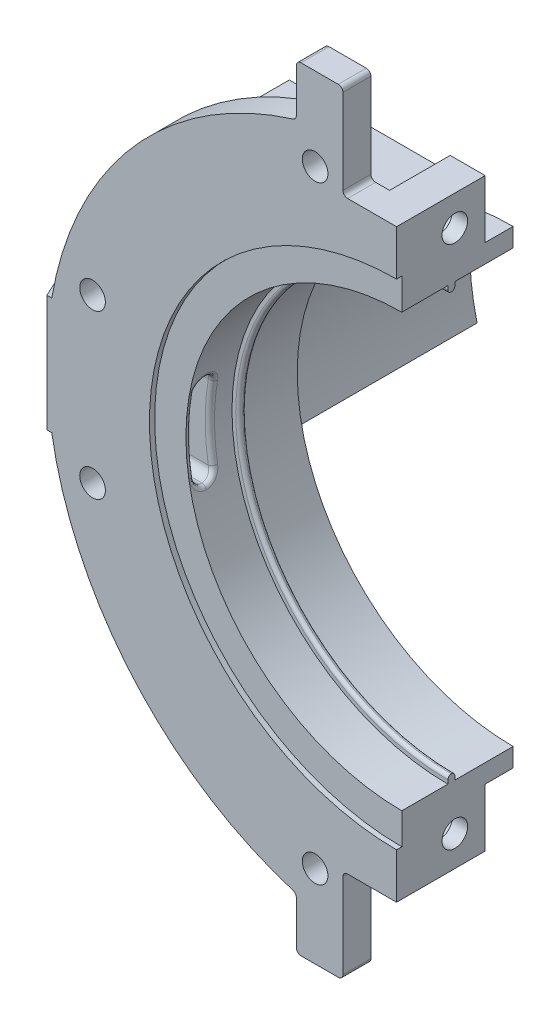
SolidWorks part; units mm, degrees
ref_plane "Front" through (0, 0, 0) normal (0, 0, 1) x (1, 0, 0)
ref_plane "Top" through (0, 0, 0) normal (0, 1, 0) x (1, 0, 0)
ref_plane "Right" through (0, 0, 0) normal (1, 0, 0) x (0, 0, -1)
sketch "Sketch1" plane through (0, 0, 0) normal (0, 0, 1) x (1, 0, 0)
  line L1 (0, 0) -> (180, 0)
  line L2 (0, 0) -> (0, 180)
  line L3 (0, 180) -> (180, 180)
  line L4 (180, 0) -> (180, 180)
  dimension "D1" = 180
extrude "Boss-Extrude1" add sketch "Sketch1" along normal blind 6
sketch "Sketch2" plane through (0, 0, 0) normal (0, 0, -1) x (-1, 0, 0)
  line L0 (0, 90) -> (-180, 90) construction
  line L1 (0, 180) -> (0, 0) construction
  line L3 (-180, 0) -> (-180, 180) construction
  circle A0 centre (-90, 90) radius 46.3
  circle A1 centre (-90, 90) radius 50.3
  point P11 (-90, 90)
  dimension "D1" = 92.6
  dimension "D2" = 4
extrude "Boss-Extrude2" add sketch "Sketch2" along normal blind 19
sketch "Sketch3" plane through (0, 0, 0) normal (0, 0, -1) x (-1, 0, 0)
  circle A0 centre (-90, 90) radius 46.3
  dimension "D1" = 92.6
extrude "Cut-Extrude1" cut sketch "Sketch3" against normal up to next
sketch "Sketch4" plane through (0, 0, 0) normal (0, 0, -1) x (-1, 0, 0)
  line L0 (0, 77.5) -> (0, 102.5)
  line L1 (0, 180) -> (0, 0) construction
  line L2 (0, 77.5) -> (-41.2779, 77.5)
  line L3 (0, 102.5) -> (-41.2779, 102.5)
  circle A0 centre (-90, 90) radius 50.3 construction
  arc A1 (-41.2779, 77.5) -> (-41.2779, 102.5) centre (-90, 90) ccw
  point P2 (0, 90)
  point P5 (0, 90)
  dimension "D1" = 25
extrude "Boss-Extrude3" add sketch "Sketch4" along normal blind 60
ref_plane "Plane1" through (0, 90, 0) normal (0, -1, 0) x (-1, 0, 0)
sketch "Sketch7" plane through (0, 0, 0) normal (0, 0, -1) x (-1, 0, 0)
  circle A0 centre (-90, 90) radius 46.3 construction
  circle A1 centre (-90, 90) radius 46.3 construction
  circle A2 centre (-90, 90) radius 46.3
  circle A3 centre (-90, 90) radius 46.3
sketch "Sketch6" plane through (0, 90, 0) normal (0, -1, 0) x (-1, 0, 0)
  line L0 (-51.2779, -3.75) -> (-40, -3.75)
  line L1 (-40, -3.75) -> (-4, 21.25)
  line L2 (-51.2779, 0.25) -> (-37.2779, 0.25)
  line L3 (-37.2779, 60) -> (-37.2779, 0.25)
  line L4 (-51.2779, 0.25) -> (-51.2779, -3.75)
  line L5 (-4, 21.25) -> (-4, 60)
  line L6 (-41.2779, 60) -> (0, 60) construction
  line L7 (-4, 60) -> (-37.2779, 60)
  line L8 (0, 60) -> (0, 0) construction
  line L9 (-41.2779, 60) -> (-41.2779, 19) construction
  line L10 (-43.7, 19) -> (-136.3, 19) construction
  dimension "D1" = 4
  dimension "D2" = 4
  dimension "D3" = 4
  dimension "D4" = 18.75
  dimension "D5" = 36
  dimension "D6" = 14
  dimension "D7" = 25
extrude "Cut-Extrude2" cut sketch "Sketch6" against normal mid plane 20
fillet "Fillet2" radius 5 2 edges at (4, 90, -21.25) (40, 90, 3.75)
fillet "Fillet3" radius 2 15 edges at (22.4309, 100, -8.4507) (40.0716, 100, 3.5215) (22.4309, 80, -8.4507) (40.0716, 80, 3.5215) (41.0354, 80, -0.25) (41.0354, 100, -0.25) (43.1793, 100, 3.75) (43.1793, 80, 3.75) (4, 100, -41.9326) (4.5694, 100, -21.5478) (4, 80, -41.9326) (4.5694, 80, -21.5478) (37.2779, 100, -30.125) (37.2779, 80, -30.125) (37.2779, 90, -0.25)
fillet "Fillet4" radius 3 2 edges at (41.2779, 77.5, -9.5) (41.2779, 102.5, -9.5)
hole_wizard "M5 Clearance Hole1" positions "Sketch11" profile "Sketch12" hole size "M5" standard "ANSI Metric" end condition up to next
sketch "Sketch11" plane through (0, 0, 0) normal (0, 0, -1) x (-1, 0, 0)
  point P52 (-107.4703, 155.2)
  point P58 (-155.2, 107.4703)
  point P61 (-155.2, 72.5297)
  point P67 (-107.4703, 24.8)
  point P70 (-72.5297, 24.8)
  point P76 (-24.8, 72.5297)
  point P79 (-24.8, 107.4703)
  point P85 (-72.5297, 155.2)
sketch "Sketch12" plane through (107.4703, 155.2, 0) normal (1, 0, 0) x (0, 1, 0)
  line L0 (0, 0) -> (0, 6)
  line L1 (0, 6) -> (2.75, 6)
  line L2 (2.75, 6) -> (2.75, 0)
  line L5 (2.75, 0) -> (0, 0)
  line L11 (0, -6.35) -> (0, 107.95) construction
  dimension "Thru Hole Dia." = 5.5
  dimension "Thru Hole Depth" = 6
sketch "Sketch15" plane through (0, 0, 0) normal (0, 0, -1) x (-1, 0, 0)
  line L0 (-180, 90) -> (-90, 90) construction
  line L3 (-180, 0) -> (-180, 180) construction
  line L4 (-137.3, 93.5) -> (-137.3, 86.5)
  line L5 (-137.3, 93.5) -> (-162.3, 93.5)
  line L6 (-162.3, 93.5) -> (-162.3, 86.5)
  line L7 (-137.3, 86.5) -> (-162.3, 86.5)
  line L8 (-93.5, 42.7) -> (-86.5, 36.7) construction
  line L9 (-93.5, 36.7) -> (-86.5, 42.7) construction
  arc A0 (-41.8739, 104.6276) -> (-41.8739, 75.3724) centre (-90, 90) ccw construction
  point P4 (-137.3, 90)
  point P6 (-90, 39.7)
  dimension "D1" = 7
  dimension "D2" = 25
  dimension "D3" = 47.3
extrude "Boss-Extrude5" add sketch "Sketch15" along normal blind 19
ref_plane "Plane2" through (0, 90, 0) normal (0, 1, 0) x (0, 0, -1)
sketch "Sketch17" plane through (0, 90, 0) normal (0, 1, 0) x (0, 0, -1)
  line L6 (-1.0441, -134.6888) -> (19, -154.733)
  line L8 (19, -140.1781) -> (19, -162.3) construction
  line L9 (19, -154.733) -> (19, -159.233)
  line L10 (19, -159.233) -> (-5.5441, -134.6888)
  line L11 (-5.5441, -134.6888) -> (-1.0441, -134.6888)
  dimension "D1" = 4.5
  dimension "D2" = 4.5
extrude "Cut-Extrude3" cut sketch "Sketch17" against normal mid plane 4 contours L6 L9 L10 | L11 L10 L9 L6 region at (145.8738, 90, -7.8151)
fillet "Fillet5" radius 1.5 4 edges at (145.4949, 92, -9.7619) (145.4949, 88, -9.7619) (147.7449, 92, -7.5119) (147.7449, 88, -7.5119)
sketch "Sketch30" plane through (0, 90, 0) normal (0, -1, 0) x (-1, 0, 0)
  line L1 (22.1625, 78.3225) -> (-206.3555, 78.3225)
  line L2 (22.1625, 78.3225) -> (22.1625, -34.6262)
  line L3 (22.1625, -34.6262) -> (-206.3555, -34.6262)
  line L4 (-206.3555, 78.3225) -> (-206.3555, -34.6262)
sketch "Sketch31" plane through (0, 0, 6) normal (0, 0, 1) x (1, 0, 0)
  line L2 (0, 180) -> (0, 0) construction
  line L3 (0, 0) -> (180, 0) construction
  line L4 (180, 0) -> (180, 180) construction
  line L5 (180, 180) -> (0, 180) construction
  line L8 (0, 180) -> (0, 102.5)
  line L9 (0, 0) -> (180, 0)
  line L10 (180, 0) -> (180, 180)
  line L11 (180, 180) -> (0, 180)
  line L12 (0, 77.5) -> (0, 0)
  line L13 (41.2779, 77.5) -> (0, 77.5) construction
  line L14 (0, 102.5) -> (41.2779, 102.5) construction
  line L15 (16.049, 77.5) -> (0, 77.5)
  line L16 (0, 102.5) -> (16.049, 102.5)
  circle A4 centre (90, 90) radius 75 construction
  arc A5 (16.049, 77.5) -> (16.049, 102.5) centre (90, 90) ccw
extrude "Cut-Extrude4" cut sketch "Sketch31" against normal up to next contours A5 L16 L8 L11 L10 L9 L12 L15
sketch "Sketch33" plane through (0, 0, 6) normal (0, 0, 1) x (1, 0, 0)
  line L1 (0, 102.5) -> (1, 102.5)
  line L2 (0, 102.5) -> (0, 77.5)
  line L3 (0, 77.5) -> (1, 77.5)
  line L4 (1, 102.5) -> (1, 77.5)
  dimension "D1" = 1
extrude "Cut-Extrude5" cut sketch "Sketch33" against normal up to next
sketch "Sketch35" plane through (0, 0, 0) normal (0, 0, -1) x (-1, 0, 0)
  line L0 (-90, 15) -> (-90, 165) construction
  line L4 (-97.5, 152.7377) -> (-82.5, 152.7377)
  line L5 (-97.5, 152.7377) -> (-97.5, 139.7377)
  line L6 (-97.5, 139.7377) -> (-82.5, 139.7377)
  line L7 (-82.5, 152.7377) -> (-82.5, 139.7377)
  line L8 (-97.5, 40.2623) -> (-82.5, 40.2623)
  line L9 (-97.5, 40.2623) -> (-97.5, 27.2623)
  line L10 (-97.5, 27.2623) -> (-82.5, 27.2623)
  line L11 (-82.5, 40.2623) -> (-82.5, 27.2623)
  arc A0 (-16.049, 102.5) -> (-16.049, 77.5) centre (-90, 90) ccw construction
  arc A1 (-41.8739, 104.6276) -> (-140.1781, 93.5) centre (-90, 90) ccw construction
  arc A2 (-140.1781, 86.5) -> (-41.8739, 75.3724) centre (-90, 90) ccw construction
  point P8 (-90, 90)
  point P18 (-90, 152.7377)
  point P26 (-90, 27.2623)
  dimension "D1" = 15
  dimension "D2" = 13
  dimension "D3" = 13
  dimension "D4" = 15
extrude "Boss-Extrude6" add sketch "Sketch35" along normal blind 13
hole_wizard "M5 Clearance Hole2" positions "Sketch38" profile "Sketch39" hole size "M5" standard "ANSI Metric" end condition through all
sketch "Sketch38" plane through (97.5, 0, 0) normal (1, 0, 0) x (0, 0, -1)
  line L0 (13, 152.7377) -> (0, 152.7377) construction
  line L1 (13, 40.2623) -> (13, 27.2623) construction
  line L2 (13, 152.7377) -> (13, 139.7377) construction
  point P0 (6.5, 146.2377)
  point P3 (6.5, 33.7623)
  point P8 (6.5, 152.7377)
  point P12 (13, 33.7623)
  point P15 (13, 146.2377)
sketch "Sketch39" plane through (97.5, 146.2377, -6.5) normal (0, 1, 0) x (0, 0, -1)
  line L0 (0, 0) -> (0, 96.5)
  line L1 (0, 96.5) -> (2.75, 96.5)
  line L2 (2.75, 96.5) -> (2.75, 0)
  line L5 (2.75, 0) -> (0, 0)
  line L11 (0, -6.35) -> (0, 107.95) construction
  dimension "Thru Hole Dia." = 5.5
  dimension "Thru Hole Depth" = 96.5
sketch "Sketch40" plane through (82.5, 0, 0) normal (-1, 0, 0) x (0, 0, 1)
  line L0 (-13, 139.7377) -> (-13, 152.7377) construction
  line L1 (-10.5, 143.9283) -> (-6.5, 141.6189)
  line L2 (-6.5, 141.6189) -> (-2.5, 143.9283)
  line L3 (-2.5, 143.9283) -> (-2.5, 148.5471)
  line L4 (-2.5, 148.5471) -> (-6.5, 150.8565)
  line L5 (-6.5, 150.8565) -> (-10.5, 148.5471)
  line L6 (-10.5, 148.5471) -> (-10.5, 143.9283)
  line L7 (-13, 27.2623) -> (-13, 139.7377) construction
  line L8 (-2.5, 31.4529) -> (-2.5, 36.0717)
  line L9 (-2.5, 36.0717) -> (-6.5, 38.3811)
  line L10 (-6.5, 38.3811) -> (-10.5, 36.0717)
  line L11 (-10.5, 36.0717) -> (-10.5, 31.4529)
  line L12 (-10.5, 31.4529) -> (-6.5, 29.1435)
  line L13 (-6.5, 29.1435) -> (-2.5, 31.4529)
  circle A0 centre (-6.5, 146.2377) radius 4 construction
  circle A1 centre (-6.5, 33.7623) radius 4 construction
  dimension "D1" = 8
  dimension "D2" = 8
extrude "Cut-Extrude6" cut sketch "Sketch40" against normal blind 4.2
sketch "Sketch41" plane through (0, 0, 0) normal (0, 0, -1) x (-1, 0, 0)
  line L0 (-90, 15) -> (-90, 165) construction
  line L2 (22.1625, 90) -> (-206.3555, 90) construction
  line L3 (-101.5, 152.7377) -> (-78.5, 152.7377)
  line L4 (-101.5, 152.7377) -> (-101.5, 167.7377)
  line L5 (-101.5, 167.7377) -> (-78.5, 167.7377)
  line L6 (-78.5, 152.7377) -> (-78.5, 167.7377)
  line L7 (-14.4828, 90) -> (-165.5172, 90) construction
  line L8 (-78.5, 27.2623) -> (-78.5, 12.2623)
  line L9 (-101.5, 12.2623) -> (-78.5, 12.2623)
  line L10 (-101.5, 27.2623) -> (-101.5, 12.2623)
  line L11 (-101.5, 27.2623) -> (-78.5, 27.2623)
  line L14 (-82.5, 152.7377) -> (-97.5, 152.7377) construction
  arc A0 (-16.049, 102.5) -> (-16.049, 77.5) centre (-90, 90) ccw construction
  point P7 (-90, 90)
  point P15 (-90, 152.7377)
  point P24 (-90, 90)
  dimension "D1" = 15
  dimension "D2" = 23
extrude "Cut-Extrude7" cut sketch "Sketch41" against normal up to next
fillet "Fillet8" radius 1 4 edges at (101.5, 164.1131, 3) (78.5, 164.1131, 3) (101.5, 15.8869, 3) (78.5, 15.8869, 3)
sketch "Sketch42" plane through (0, 102.5, 0) normal (0, 1, 0) x (1, 0, 0)
  line L0 (15, -6) -> (1, 24)
  line L1 (165, -6) -> (15, -6) construction
  line L2 (1, -6) -> (16.049, -6) construction
  line L3 (1, 60) -> (1, -6) construction
  line L4 (1, 24) -> (1, -6)
  line L5 (1, -6) -> (15, -6)
  dimension "D1" = 30
  dimension "D2" = 14
extrude "Cut-Extrude8" cut sketch "Sketch42" against normal up to next
ref_plane "Plane3" through (90, 0, 0) normal (1, 0, 0) x (0, 0, -1)
sketch "Sketch43" plane through (90, 0, 0) normal (1, 0, 0) x (0, 0, -1)
  line L1 (-26.2287, 173.6103) -> (66.8607, 173.6103)
  line L2 (-26.2287, 173.6103) -> (-26.2287, 11.2507)
  line L3 (-26.2287, 11.2507) -> (66.8607, 11.2507)
  line L4 (66.8607, 173.6103) -> (66.8607, 11.2507)
sketch "Sketch46" plane through (0, 0, 0) normal (0, 0, -1) x (-1, 0, 0)
  line L0 (-101.5, 162.9366) -> (-101.5, 172.9366)
  line L1 (-101.5, 172.9366) -> (-111.5, 172.9366)
  line L2 (-111.5, 172.9366) -> (-111.5, 161.8523)
  line L9 (-101.5, 152.7377) -> (-101.5, 162.9366)
  line L10 (-101.5, 17.0634) -> (-101.5, 27.2623)
  line L11 (-101.5, 27.2623) -> (-97.5, 27.2623)
  line L12 (-97.5, 27.2623) -> (-97.5, 40.2623)
  line L13 (-140.1781, 86.5) -> (-162.3, 86.5)
  line L14 (-162.3, 86.5) -> (-162.3, 93.5)
  line L15 (-162.3, 93.5) -> (-140.1781, 93.5)
  line L16 (-97.5, 139.7377) -> (-97.5, 152.7377)
  line L17 (-97.5, 152.7377) -> (-101.5, 152.7377)
  line L18 (-101.5, 152.7377) -> (-101.5, 162.9366)
  line L19 (-101.5, 17.0634) -> (-101.5, 27.2623)
  line L20 (-101.5, 27.2623) -> (-97.5, 27.2623)
  line L21 (-97.5, 27.2623) -> (-97.5, 40.2623)
  line L22 (-140.1781, 86.5) -> (-162.3, 86.5)
  line L23 (-162.3, 86.5) -> (-162.3, 93.5)
  line L24 (-162.3, 93.5) -> (-140.1781, 93.5)
  line L25 (-97.5, 139.7377) -> (-97.5, 152.7377)
  line L26 (-97.5, 152.7377) -> (-101.5, 152.7377)
  arc A5 (-101.5, 162.9366) -> (-102.6689, 163.9222) centre (-102.5, 162.9366) ccw
  arc A6 (-102.6689, 163.9222) -> (-102.6689, 16.0778) centre (-90, 90) ccw
  arc A7 (-102.6689, 16.0778) -> (-101.5, 17.0634) centre (-102.5, 17.0634) ccw
  arc A8 (-140.1781, 86.5) -> (-97.5, 40.2623) centre (-90, 90) ccw
  arc A9 (-97.5, 139.7377) -> (-140.1781, 93.5) centre (-90, 90) ccw
  arc A10 (-101.5, 162.9366) -> (-102.6689, 163.9222) centre (-102.5, 162.9366) ccw
  arc A11 (-102.6689, 163.9222) -> (-102.6689, 16.0778) centre (-90, 90) ccw
  arc A12 (-102.6689, 16.0778) -> (-101.5, 17.0634) centre (-102.5, 17.0634) ccw
  arc A13 (-140.1781, 86.5) -> (-97.5, 40.2623) centre (-90, 90) ccw
  arc A14 (-97.5, 139.7377) -> (-140.1781, 93.5) centre (-90, 90) ccw
  arc M18 (-101.5, 162.9366) -> (-102.6689, 163.9222) centre (-102.5, 162.9366) ccw
  arc M19 (-102.6689, 163.9222) -> (-102.6689, 16.0778) centre (-90, 90) ccw
  dimension "D2" = 10
  dimension "D3" = 10
  dimension "D1" = 0
extrude "Boss-Extrude8" add sketch "Sketch46" against normal up to surface (6 mm away) contours L1 L2 L0 M19 M18 region at (106.6758, 167.9846, 0) up to face at (74.0539, 90, 6)
ref_plane "Plane5" through (90, 0, 0) normal (1, 0, 0) x (0, 0, -1)
mirror "Mirror2" about plane through (90, 0, 0) normal (1, 0, 0) of "Boss-Extrude8"
ref_plane "Plane4" through (0, 90, 0) normal (0, 1, 0) x (1, 0, 0)
mirror "Mirror1" about plane through (0, 90, 0) normal (0, 1, 0) of "Mirror2", "Boss-Extrude8"
fillet "Fillet10" radius 1 16 edges at (111.5, 161.8523, 3) (111.5, 172.9366, 3) (101.5, 172.9366, 3) (101.5, 152.7377, 3) (101.5, 27.2623, 3) (101.5, 7.0634, 3) (111.5, 7.0634, 3) (111.5, 18.1477, 3) (68.5, 161.8523, 3) (68.5, 172.9366, 3) (78.5, 152.7377, 3) (78.5, 172.9366, 3) (68.5, 18.1477, 3) (68.5, 7.0634, 3) (78.5, 7.0634, 3) (78.5, 27.2623, 3)
sketch "Sketch47" plane through (0, 0, 6) normal (0, 0, 1) x (1, 0, 0)
  circle A0 centre (90, 90) radius 53
  dimension "D1" = 106
extrude "Cut-Extrude10" cut sketch "Sketch47" against normal blind 1.12
ref_plane "Plane6" through (0, 0, -5) normal (0, 0, 1) x (1, 0, 0)
sketch "Sketch49" plane through (0, 0, -5) normal (0, 0, 1) x (1, 0, 0)
  circle A0 centre (90, 90) radius 46.3
  circle A1 centre (90, 90) radius 44.75
  dimension "D1" = 92.6
  dimension "D2" = 89.5
extrude "Boss-Extrude9" add sketch "Sketch49" against normal blind 1.5
fillet "Fillet11" radius 0.75 2 edges at (134.75, 90, -5) (134.75, 90, -6.5)
sketch "Sketch50" plane through (0, 0, -5) normal (0, 0, 1) x (1, 0, 0)
  line L0 (132.7756, 107.7182) -> (90, 90)
  line L1 (90, 90) -> (132.7756, 72.2818)
  line L2 (162.3, 86.5) -> (140.1781, 86.5) construction
  arc A0 (132.7756, 72.2818) -> (132.7756, 107.7182) centre (90, 90) ccw
  circle A2 centre (90, 90) radius 46.3 construction
  dimension "D1" = 46.3
  dimension "D2" = 45
  dimension "D3" = 22.5
extrude "Cut-Extrude11" [suppressed] cut sketch "Sketch50" against normal up to next
pattern_circular "CirPattern1" [suppressed] count 4 over 360 of bodies 147
fillet "Fillet12" radius 1 6 edges at (44.6367, 80.7339, 0.2018) (44.7016, 80.4217, 2.9784) (44.6367, 99.2661, 3.2982) (44.7016, 99.5783, 0.5216) (43.7, 90, -0.25) (43.7, 90, 3.75)
sketch "Sketch51" plane through (0, 0, -13) normal (0, 0, -1) x (-1, 0, 0)
  line L0 (-82.5, 152.7377) -> (-97.5, 152.7377) construction
  line L1 (-90, 190) -> (-180, 190)
  line L2 (-90, 190) -> (-90, -10)
  line L3 (-90, -10) -> (-180, -10)
  line L4 (-180, 190) -> (-180, -10)
  line L5 (-162.3, 93.5) -> (-162.3, 86.5) construction
  point P6 (-90, 152.7377)
  point P7 (-162.3, 90)
  point P10 (-180, 90)
  dimension "D1" = 90
  dimension "D2" = 200
extrude "Cut-Extrude12" cut sketch "Sketch51" against normal through all both and the other way through all
